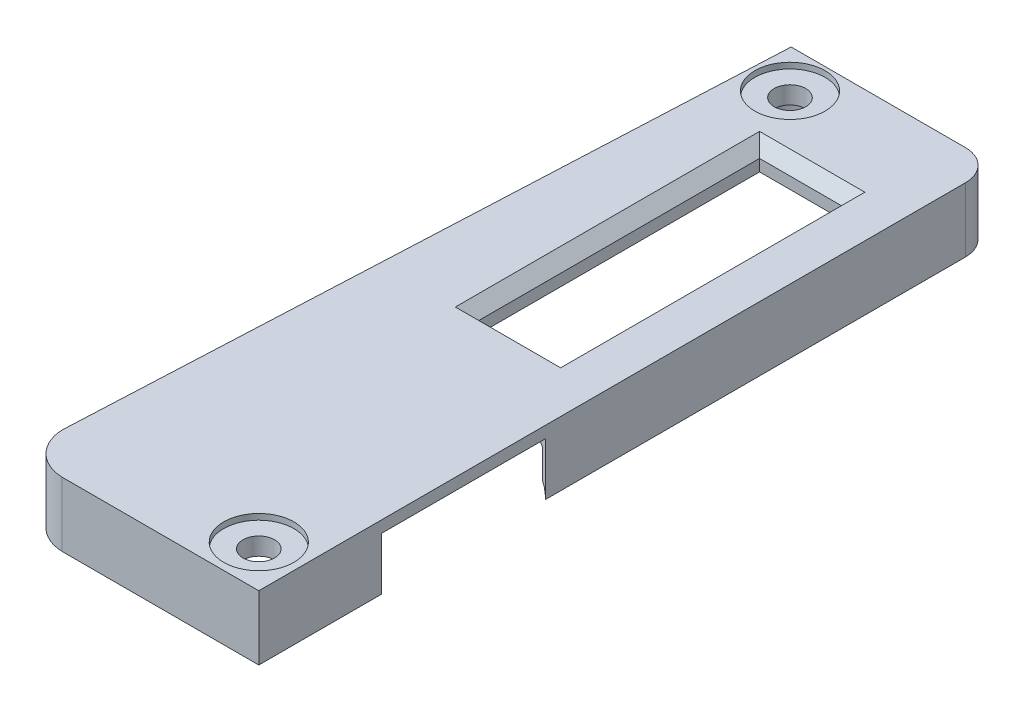
SolidWorks part; units mm, degrees
ref_plane "前视基准面" through (0, 0, 0) normal (0, 0, 1) x (1, 0, 0)
ref_plane "上视基准面" through (0, 0, 0) normal (0, 1, 0) x (1, 0, 0)
ref_plane "右视基准面" through (0, 0, 0) normal (1, 0, 0) x (0, 0, -1)
other "Configuration Table"
sketch "草图1" plane through (0, 0, 0) normal (0, 1, 0) x (1, 0, 0)
  line L0 (0, 3.3) -> (11.7, 3.3)
  line L1 (14.3, 0.7) -> (14.3, -59.7)
  line L2 (14.3, -59.7) -> (-3.3, -59.7)
  line L3 (-3.3, -59.7) -> (-3.3, 0)
  line L4 (-3.3, 0) -> (-3.3, 3.3)
  line L5 (-3.3, 3.3) -> (0, 3.3)
  circle A0 centre (0, 0) radius 1.35
  circle A1 centre (0, 0) radius 3.3 construction
  arc A2 (14.3, 0.7) -> (11.7, 3.3) centre (11.7, 0.7) ccw
  circle A3 centre (10.7, -56.1) radius 1.35
  dimension "D1" = 2.7
  dimension "D2" = 6.6
  dimension "D3" = 14.3
  dimension "D4" = 2.6
  dimension "D6" = 10.7
  dimension "D7" = 56.1
  dimension "D5" = 63
extrude "凸台-拉伸1" add sketch "草图1" along normal blind 2
sketch "草图2" plane through (0, 2, 0) normal (0, 1, 0) x (1, 0, 0)
  line L0 (-3.3, 1.1799) -> (-6.1716, -59.7)
  line L1 (-3.3, 1.1799) -> (-3.3, -59.7)
  line L2 (-6.0014, -56.0919) -> (-3.2, 3.3) construction
  line L4 (-3.3, -59.7) -> (-6.1716, -59.7)
  line L7 (-3.3, 3.3) -> (-3.3, -59.7) construction
  point P3 (-3.3, -59.7)
extrude "凸台-拉伸2" add sketch "草图2" against normal up to surface (2 mm away) up to face at (6.8477, 0, 22.3123)
sketch "草图3" plane through (0, 2, 0) normal (0, 1, 0) x (1, 0, 0)
  line L0 (-3.3, 1.1799) -> (-3.2, 3.3)
  line L1 (11.7, 3.3) -> (-3.3, 3.3) construction
  line L2 (-3.2, 3.3) -> (-3.3, 3.3)
  line L3 (-3.3, 3.3) -> (-3.3, 1.1799)
  line L4 (-3.3, 1.1799) -> (-6.1716, -59.7) construction
  line L5 (-2.3, -59.7) -> (-6.1716, -59.7)
  line L6 (-6.1716, -59.7) -> (-6.0014, -56.0919)
  arc A0 (-6.0014, -56.0919) -> (-2.3, -59.7) centre (-2.4, -56.1) ccw construction
  arc A1 (-6.0014, -56.0919) -> (-2.3, -59.7) centre (-2.4, -56.1) ccw
  line M3 (11.7, 3.3) -> (-3.3, 3.3)
  line M4 (-3.3, 3.3) -> (-3.3, 1.1799)
  line M5 (-3.3, 1.1799) -> (-6.1716, -59.7)
  line M6 (-6.1716, -59.7) -> (14.3, -59.7)
extrude "切除-拉伸1" cut sketch "草图3" against normal through all and the other way through all contours L0 M4 M3 | A1 M5 M6 region at (-3.2667, 2, -2.5933) region at (-5.2842, 2, 58.8559)
sketch "草图4" plane through (0, 0, 0) normal (0, -1, 0) x (1, 0, 0)
  line L21 (12.8, -0.7) -> (12.8, 58.2)
  line L22 (12.8, 58.2) -> (-2.4764, 58.2)
  line L23 (-4.5013, 56.1245) -> (-1.7691, -1.8)
  line L24 (-1.7691, -1.8) -> (11.7, -1.8)
  line L25 (12.8, -0.7) -> (12.8, 54.3245)
  line L26 (8.9245, 58.2) -> (-2.4764, 58.2)
  line L27 (-4.5013, 56.1245) -> (-1.9457, 1.9434)
  line L28 (2.0791, -1.8) -> (11.7, -1.8)
  line L33 (-6.0014, 56.0919) -> (-3.2, -3.3)
  line L34 (-3.2, -3.3) -> (11.7, -3.3)
  line L35 (14.3, -0.7) -> (14.3, 59.7)
  line L36 (14.3, 59.7) -> (-2.5, 59.7)
  line L37 (-6.0014, 56.0919) -> (-3.2, -3.3)
  line L38 (-3.2, -3.3) -> (11.7, -3.3)
  line L39 (14.3, -0.7) -> (14.3, 59.7)
  line L40 (14.3, 59.7) -> (-2.5, 59.7)
  arc A7 (11.7, -1.8) -> (12.8, -0.7) centre (11.7, -0.7) ccw
  arc A8 (-2.4764, 58.2) -> (-4.5013, 56.1245) centre (-2.4, 56.1) ccw
  arc A9 (11.7, -1.8) -> (12.8, -0.7) centre (11.7, -0.7) ccw
  arc A10 (-2.4764, 58.2) -> (-4.5013, 56.1245) centre (-2.4, 56.1) ccw
  arc A13 (11.7, -3.3) -> (14.3, -0.7) centre (11.7, -0.7) ccw
  arc A14 (-2.5, 59.7) -> (-6.0014, 56.0919) centre (-2.4, 56.1) ccw
  arc A15 (11.7, -3.3) -> (14.3, -0.7) centre (11.7, -0.7) ccw
  arc A16 (-2.5, 59.7) -> (-6.0014, 56.0919) centre (-2.4, 56.1) ccw
  circle A21 centre (10.7, 56.1) radius 2.75
  arc A22 (12.8, 54.3245) -> (8.9245, 58.2) centre (10.7, 56.1) ccw
  circle A24 centre (0, 0) radius 2.75
  arc A25 (-1.9457, 1.9434) -> (2.0791, -1.8) centre (0, 0) ccw
  dimension "D1" = 1.5
  dimension "D2" = 0
  dimension "D3" = 0.5
  dimension "D4" = 0.5
extrude "凸台-拉伸3" add sketch "草图4" along normal up to surface (3.5 mm away)
sketch "草图5" plane through (14.3, 0, 0) normal (1, 0, 0) x (0, 0, -1)
  line L0 (-59.7, -3.5) -> (0.7, -3.5) construction
  line L1 (-35.2, -3.5) -> (-49.2, -3.5)
  line L2 (-35.2, -3.5) -> (-35.2, 1)
  line L3 (-35.2, 1) -> (-49.2, 1)
  line L4 (-49.2, -3.5) -> (-49.2, 1)
  line L5 (-35.2, -3.5) -> (-49.2, 1) construction
  line L6 (-35.2, 1) -> (-49.2, -3.5) construction
  line L7 (-42.2, 0.55) -> (-42.2, -3.5) construction
  line L8 (-34.0108, 0.55) -> (-50.3892, 0.55) construction
  point P4 (-42.2, -1.25)
  point P12 (-42.2, -1.0315)
  point P13 (-35.5029, -3.5)
  point P14 (0, 0)
  dimension "D1" = 14
  dimension "D2" = 4.5
extrude "切除-拉伸2" cut sketch "草图5" against normal blind 9
sketch "草图6" plane through (0, -3.5, 0) normal (0, -1, 0) x (1, 0, 0)
  line L0 (2.1586, 33.5397) -> (2.1586, 50.8603)
  arc A0 (2.1586, 33.5397) -> (2.1586, 50.8603) centre (7.1586, 42.2) ccw
  dimension "D1" = 20
  dimension "D2" = 5
extrude "切除-拉伸3" cut sketch "草图6" against normal up to surface (4.5 mm away) up to face at (9.8, 1, 42.2)
sketch "草图7" plane through (0, 0, 0) normal (0, -1, 0) x (1, 0, 0)
  line L0 (1.3, 17.3) -> (10.6, 17.3) construction
  line L1 (12.8, 2.6) -> (1.3, 2.6) construction
  line L2 (12.8, 2.6) -> (12.8, 30.6) construction
  line L3 (12.8, 30.6) -> (1.3, 30.6) construction
  line L4 (1.3, 2.6) -> (1.3, 30.6) construction
  line L5 (12.8, 2.6) -> (1.3, 30.6) construction
  line L6 (12.8, 30.6) -> (1.3, 2.6) construction
  line L7 (1.8, 30.25) -> (10.6, 30.25) construction
  line L8 (1.8, 30.25) -> (1.8, 4.35) construction
  line L9 (1.8, 4.35) -> (10.6, 4.35) construction
  line L10 (10.6, 30.25) -> (10.6, 4.35) construction
  line L11 (1.8, 30.25) -> (10.6, 4.35) construction
  line L12 (1.8, 4.35) -> (10.6, 30.25) construction
  line L13 (6.2, 30.25) -> (6.2, 4.35) construction
  line L15 (2.7, 29.3) -> (9.7, 29.3)
  line L16 (2.7, 29.3) -> (2.7, 5.3)
  line L17 (2.7, 5.3) -> (9.7, 5.3)
  line L18 (9.7, 29.3) -> (9.7, 5.3)
  line L19 (2.7, 29.3) -> (9.7, 5.3) construction
  line L20 (2.7, 5.3) -> (9.7, 29.3) construction
  point P4 (7.05, 16.6)
  point P10 (6.2, 17.3)
  point P16 (6.2, 17.3)
  point P21 (6.2, 17.3)
  dimension "D1" = 28
  dimension "D2" = 11.5
  dimension "D3" = 0.35
  dimension "D4" = 0.5
  dimension "D5" = 8.8
  dimension "D6" = 25.9
  dimension "D7" = 24
  dimension "D8" = 7
extrude "切除-拉伸4" cut sketch "草图7" against normal through all
chamfer "倒角1" distance 1 angle 45 4 edges at (6.2, 2, 29.3) (9.7, 2, 17.3) (2.7, 2, 17.3) (6.2, 2, 5.3)
sketch "草图8" plane through (0, 0, 0) normal (0, -1, 0) x (1, 0, 0)
  line L0 (-2.8917, 22) -> (0.3, 22)
  line L1 (-1.9457, 1.9434) -> (-4.5013, 56.1245) construction
  line L2 (0.3, 22) -> (0.3, 18)
  line L3 (0.3, 18) -> (-2.703, 18)
  line L4 (-2.703, 18) -> (-2.8917, 22)
  line L5 (1.3, 2.6) -> (1.3, 30.6) construction
  line L7 (-2.5143, 14) -> (0.3, 14)
  line L8 (0.3, 14) -> (0.3, 10)
  line L9 (0.3, 10) -> (-2.3257, 10)
  line L10 (-2.3257, 10) -> (-2.5143, 14)
  dimension "D1" = 1
  dimension "D2" = 4
  dimension "D3" = 4
  dimension "D4" = 10
  dimension "D5" = 4
extrude "凸台-拉伸4" add sketch "草图8" along normal offset from surface (3 mm away) 0.5 up to face at (6.7611, -3.5, 31.1962)
sketch "草图9" plane through (0, 0, 0) normal (0, -1, 0) x (1, 0, 0)
  line L0 (2.75, 0) -> (2.75, 2.6)
  line L1 (12.8, 2.6) -> (1.3, 2.6) construction
  line L3 (2.75, 2.6) -> (3.3, 2.6)
  line L4 (3.3, 2.6) -> (3.3, -1.8)
  line L5 (11.7, -1.8) -> (2.0791, -1.8) construction
  line L6 (3.3, -1.8) -> (2.0791, -1.8)
  line L7 (1.3, 2.6) -> (1.3, 30.6) construction
  arc A0 (2.0791, -1.8) -> (2.75, 0) centre (0, 0) ccw
  dimension "D1" = 2
extrude "凸台-拉伸5" add sketch "草图9" along normal up to surface (3 mm away) up to face at (-1.06, -3, 12)
chamfer "倒角2" distance 1.5 angle 45 3 edges at (0.3, -3, 12) (0.3, -3, 20) (3.025, -3, 2.6)
sketch "草图10" plane through (0, 0, 0) normal (0, -1, 0) x (1, 0, 0)
  line L0 (0.3, 22) -> (0.3, 31.6)
  line L1 (0.3, 31.6) -> (-3.3445, 31.6)
  line L2 (-1.9457, 1.9434) -> (-4.5013, 56.1245) construction
  line L3 (-3.3445, 31.6) -> (-2.8917, 22)
  line L4 (-2.8917, 22) -> (0.3, 22)
  line L5 (0.3, 18) -> (0.3, 14)
  line L6 (0.3, 14) -> (-2.5143, 14)
  line L7 (-2.5143, 14) -> (-2.703, 18)
  line L8 (-2.703, 18) -> (0.3, 18)
  line L9 (12.8, 30.6) -> (1.3, 30.6) construction
  dimension "D1" = 1
extrude "凸台-拉伸6" add sketch "草图10" along normal blind 1
sketch "草图11" plane through (0, 0, 0) normal (0, -1, 0) x (1, 0, 0)
  line L0 (0.3, 31.6) -> (12.8, 31.6)
  line L1 (12.8, 33.9432) -> (12.8, -0.7) construction
  line L2 (12.8, 31.6) -> (12.8, 33.9432)
  line L3 (0.3, 31.6) -> (-3.3445, 31.6)
  line L4 (-1.9457, 1.9434) -> (-4.5013, 56.1245) construction
  line L5 (0.3, 31.6) -> (-3.3445, 31.6) construction
  line L6 (-3.3445, 31.6) -> (-3.4388, 33.6)
  line L7 (-3.4388, 33.6) -> (2.1586, 33.6)
  line L8 (2.1586, 33.5397) -> (2.1586, 50.8603) construction
  line L9 (2.1586, 33.5397) -> (2.1586, 33.6)
  arc A0 (2.1586, 33.5397) -> (14.3, 35.2) centre (7.1586, 42.2) ccw construction
  arc A1 (2.1586, 33.5397) -> (12.8, 33.9432) centre (7.1586, 42.2) ccw
  dimension "D1" = 2
extrude "凸台-拉伸7" add sketch "草图11" along normal up to surface (1 mm away) up to face at (-1.409, -1, 26.8)
sketch "草图12" plane through (0, 2, 0) normal (0, 1, 0) x (1, 0, 0)
  circle A0 centre (0, 0) radius 3
  circle A1 centre (10.7, -56.1) radius 3
  dimension "D1" = 6
  dimension "D2" = 6
extrude "切除-拉伸5" cut sketch "草图12" against normal blind 0.5
chamfer "倒角3" distance 0.75 angle 45 2 edges at (12.6445, -3.5, 58.0445) (-1.8729, -3.5, -2.0136)
